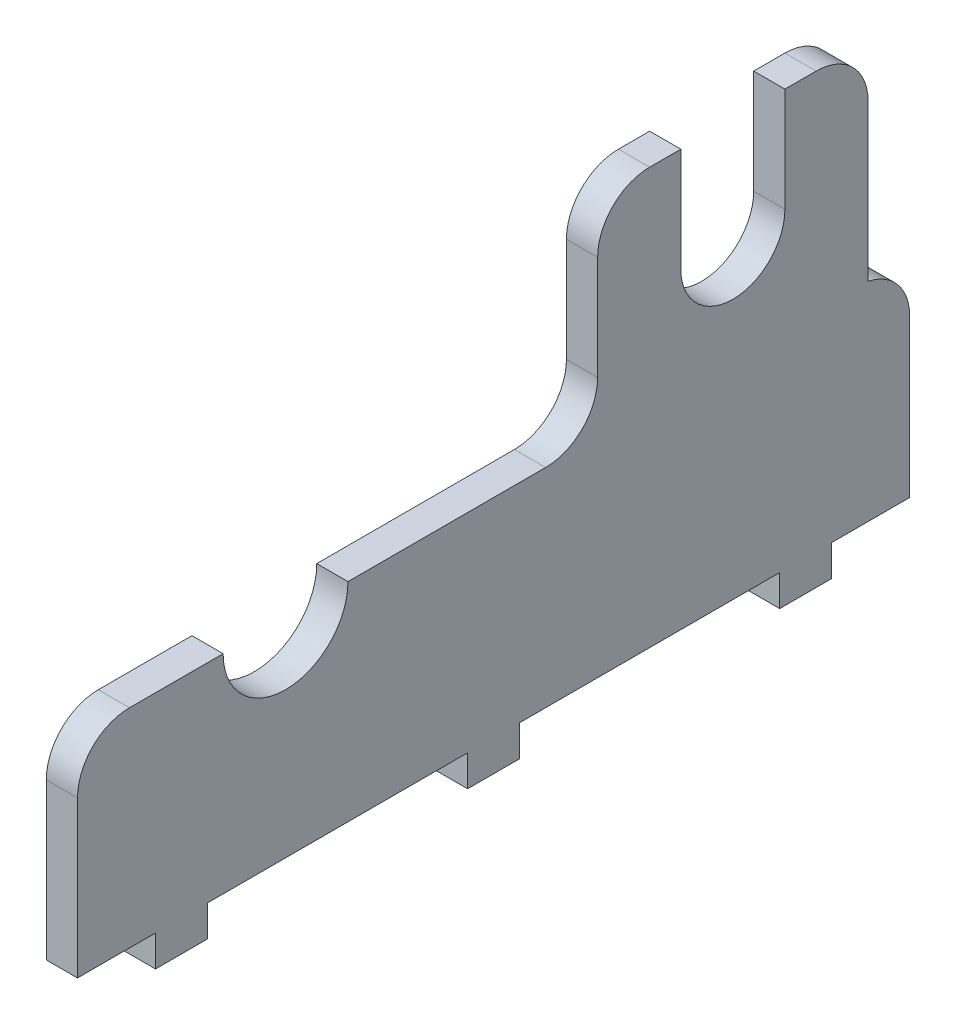
SolidWorks part; units mm, degrees
ref_plane "Front Plane" through (0, 0, 0) normal (0, 0, 1) x (1, 0, 0)
ref_plane "Top Plane" through (0, 0, 0) normal (0, 1, 0) x (1, 0, 0)
ref_plane "Right Plane" through (0, 0, 0) normal (1, 0, 0) x (0, 0, -1)
sketch "Sketch1" plane through (0, 0, 0) normal (1, 0, 0) x (0, 0, -1)
  line L0 (0, 55) -> (0, -55) construction
  line L1 (50, 0) -> (-30, 0)
  line L2 (50, 0) -> (50, 40)
  line L3 (50, 40) -> (-30, 40)
  line L4 (-30, 0) -> (-30, 40)
  line L5 (55, 0) -> (-55, 0) construction
  point P0 (0, 0)
  dimension "D2" = 30
  dimension "D1" = 80
  dimension "D4" = 40
extrude "Boss-Extrude1" add sketch "Sketch1" along normal blind 3
sketch "Sketch2" plane through (3, 0, 0) normal (1, 0, 0) x (0, 0, -1)
  line L0 (-30, 0) -> (50, 0) construction
  line L1 (-30, 40) -> (-30, 0) construction
  circle A0 centre (-10, 20) radius 6
  point P6 (-28.4862, -10)
  point P11 (28.0724, -10)
  dimension "D1" = 12
  dimension "D3" = 20
  dimension "D2" = 20
extrude "Cut-Extrude1" cut sketch "Sketch2" against normal through all
sketch "Sketch5" plane through (0, 0, 0) normal (-1, 0, 0) x (0, 0, 1)
  line L0 (-50, 40) -> (30, 40) construction
  line L2 (-28, 30) -> (-28, 40)
  line L3 (-28, 40) -> (-38, 40)
  line L4 (-38, 30) -> (-38, 40)
  line L5 (-50, 0) -> (-50, 40) construction
  line L6 (-46, 40) -> (-50, 40)
  line L7 (-20, 40) -> (31.2475, 40)
  line L8 (-20, 40) -> (-20, 20)
  line L9 (-20, 20) -> (31.2475, 20)
  line L10 (31.2475, 40) -> (31.2475, 20)
  line L11 (-46, 40) -> (-46, 20)
  line L12 (-46, 20) -> (-50, 20)
  line L13 (-50, 40) -> (-50, 20)
  arc A0 (-38, 30) -> (-28, 30) centre (-33, 30) ccw
  dimension "D1" = 10
  dimension "D2" = 43
  dimension "D3" = 13
  dimension "D4" = 13
  dimension "D5" = 10
extrude "Cut-Extrude2" cut sketch "Sketch5" against normal through all
fillet "Fillet1" radius 5 5 edges at (1.5, 20, 30) (1.5, 20, -20) (1.5, 40, -20) (1.5, 20, -50) (1.5, 40, -46)
sketch "Sketch6" plane through (0, 0, 0) normal (0, -1, 0) x (1, 0, 0)
  line L0 (0, 30) -> (0, -50) construction
  line L1 (0, 22.5) -> (3, 22.5)
  line L2 (0, 22.5) -> (0, 17.5)
  line L3 (0, 17.5) -> (3, 17.5)
  line L4 (3, 22.5) -> (3, 17.5)
  line L5 (3, 30) -> (3, -50) construction
  line L6 (3, 30) -> (0, 30) construction
  dimension "D1" = 5
  dimension "D2" = 7.5
extrude "Boss-Extrude2" add sketch "Sketch6" along normal blind 3
pattern_linear "LPattern1" count 3 spacing 30 along (0, 0, -1) of "Boss-Extrude2"
